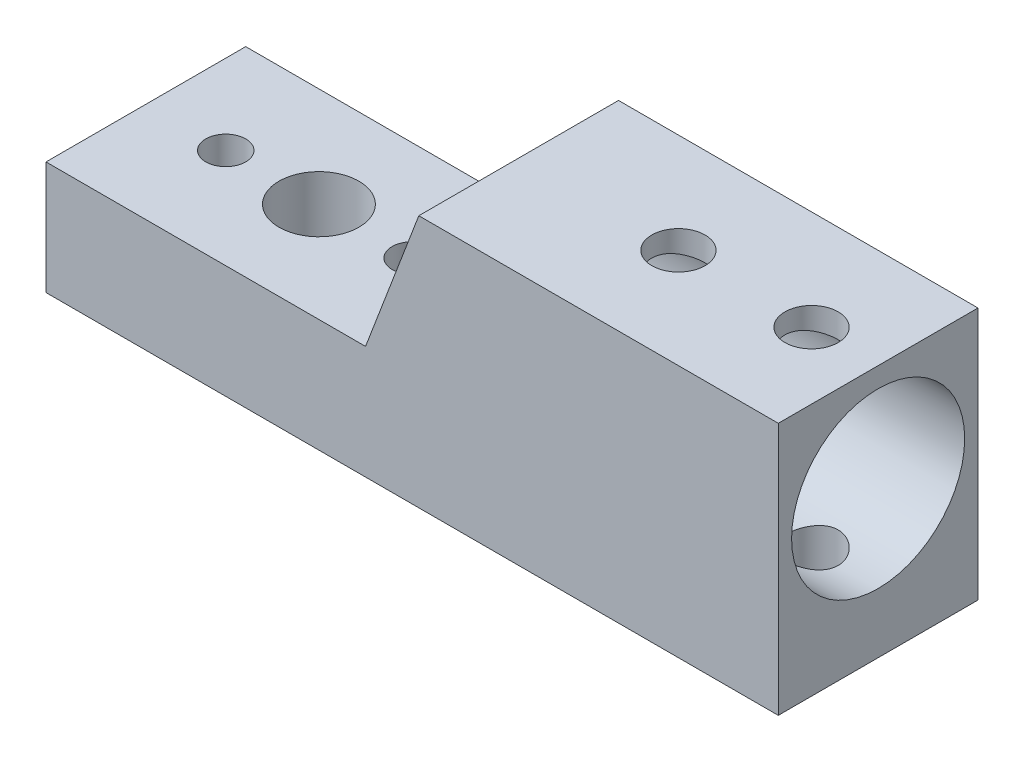
SolidWorks part; units mm, degrees
ref_plane "Front Plane" through (0, 0, 0) normal (0, 0, 1) x (1, 0, 0)
ref_plane "Top Plane" through (0, 0, 0) normal (0, 1, 0) x (1, 0, 0)
ref_plane "Right Plane" through (0, 0, 0) normal (1, 0, 0) x (0, 0, -1)
sketch "Sketch8" plane through (0, 0, 0) normal (1, 0, 0) x (0, 0, -1)
  line L1 (-6.5, -11) -> (6.5, -11)
  line L2 (-6.5, -11) -> (-6.5, 6.5)
  line L3 (-6.5, 6.5) -> (6.5, 6.5)
  line L4 (6.5, -11) -> (6.5, 6.5)
  circle A0 centre (0, 0) radius 6.5
sketch "Sketch1" plane through (0, 0, 0) normal (1, 0, 0) x (0, 0, -1)
  line L4 (7.5, -11) -> (7.5, 8)
  line L5 (-7.5, 8) -> (7.5, 8)
  line L6 (-7.5, -11) -> (7.5, -11)
  line L7 (-7.5, -11) -> (-7.5, 8)
  circle A1 centre (0, 0) radius 6.5
  point P7 (0, -11)
  dimension "D1" = 15
  dimension "D2" = 19
  dimension "D3" = 13
extrude "Boss-Extrude1" add sketch "Sketch1" along normal blind 25 contours A1 L7 L6 L4 | A1 L5 L7 | A1 L4 L5 region at (0, -10.7579, 0)
sketch "Sketch2" plane through (0, 0, 0) normal (1, 0, 0) x (0, 0, -1)
  line L8 (7.5, 8) -> (-7.5, 8)
  line L13 (7.5, 8) -> (7.5, -11)
  line L14 (7.5, -11) -> (-7.5, -11)
  line L15 (-7.5, 8) -> (-7.5, -11)
  point P0 (0, 0)
extrude "Boss-Extrude2" add sketch "Sketch2" against normal blind 2
ref_plane "Plane1" through (0, -2.5, 0) normal (0, 1, 0) x (1, 0, 0)
sketch "Sketch3" plane through (0, -2.5, 0) normal (0, 1, 0) x (1, 0, 0)
  line L0 (-30, -7.5) -> (-30, 7.5)
  line L1 (-2, -7.5) -> (-2, 7.5)
  line L11 (-30, -7.5) -> (-2, -7.5)
  line L13 (-30, 7.5) -> (-2, 7.5)
  circle A3 centre (-17, 0) radius 3
  point P2 (-9.5853, 0)
  dimension "D2" = 7.5
  dimension "D3" = 6
  dimension "D4" = 28
  dimension "D1" = 7.5
  dimension "D5" = 2
  dimension "D6" = 17
sketch "Sketch4" plane through (0, 0, 0) normal (0, 1, 0) x (1, 0, 0)
  line L0 (25, -7.5) -> (25, 7.5) construction
  circle A0 centre (10, 0) radius 2
  circle A1 centre (20, 0) radius 2
  dimension "D1" = 4
  dimension "D2" = 5
  dimension "D3" = 10
extrude "Cut-Extrude1" cut sketch "Sketch4" against normal through all both and the other way through all
extrude "Boss-Extrude3" add sketch "Sketch3" against normal blind 8.5
sketch "Sketch5" plane through (0, -11, 0) normal (0, -1, 0) x (1, 0, 0)
  circle A0 centre (-17, 0) radius 5
  dimension "D1" = 10
extrude "Cut-Extrude2" [suppressed] cut sketch "Sketch5" against normal blind 3
chamfer "Chamfer1" distance 10.5 distance2 4 1 edges at (-2, -2.5, 0) first distance on face at (-2, 2.75, 0)
sketch "Sketch6" plane through (0, -2.5, 0) normal (0, 1, 0) x (1, 0, 0)
  circle A0 centre (-24, 0) radius 1.5
  circle A2 centre (-10, 0) radius 1.5
  point P14 (-17, 0)
  dimension "D1" = 3
  dimension "D3" = 2
  dimension "D2" = 24
extrude "Cut-Extrude3" cut sketch "Sketch6" against normal through all
sketch "Sketch7" plane through (0, -11, 0) normal (0, -1, 0) x (1, 0, 0)
  line L0 (-17, 0) -> (-17, -9.5382) construction
  circle A0 centre (-10, 0) radius 3
  circle A1 centre (-24, 0) radius 3
  dimension "D1" = 6
extrude "Cut-Extrude4" cut sketch "Sketch7" against normal blind 3
